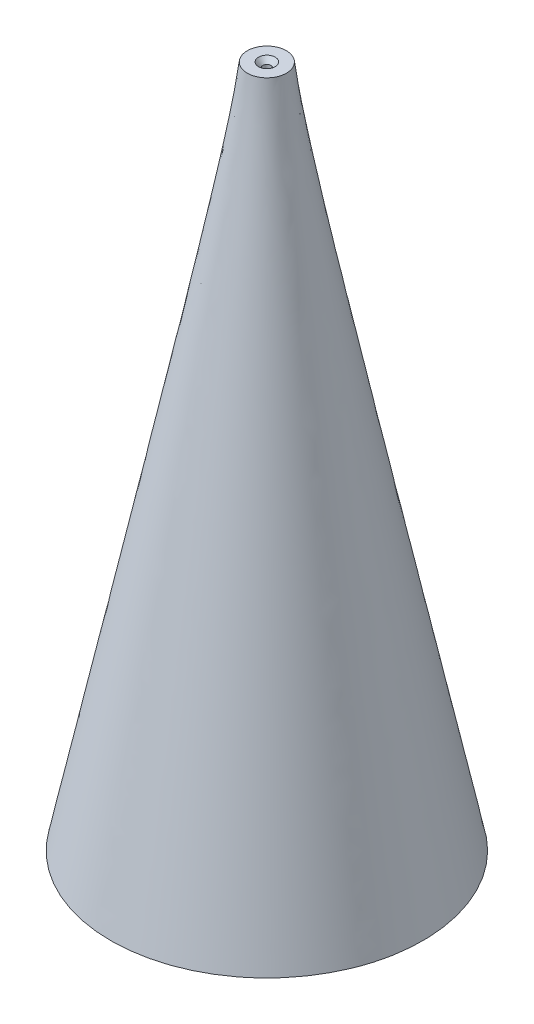
SolidWorks part; units mm, degrees
ref_plane "Front Plane" through (0, 0, 0) normal (0, 0, 1) x (1, 0, 0)
ref_plane "Top Plane" through (0, 0, 0) normal (0, 1, 0) x (1, 0, 0)
ref_plane "Right Plane" through (0, 0, 0) normal (1, 0, 0) x (0, 0, -1)
sketch "Sketch1" plane through (0, 0, 0) normal (0, 1, 0) x (1, 0, 0)
  circle A0 centre (0, 0) radius 40
  dimension "D1" = 80
ref_plane "Plane1" through (0, 100, 0) normal (0, 1, 0) x (1, 0, 0)
sketch "Sketch2" plane through (0, 100, 0) normal (0, 1, 0) x (1, 0, 0)
  circle A0 centre (0, 0) radius 5
  dimension "D1" = 10
ref_plane "Plane2" through (0, 175, 0) normal (0, 1, 0) x (1, 0, 0)
sketch "Sketch3" plane through (0, 175, 0) normal (0, 1, 0) x (1, 0, 0)
  circle A0 centre (0, 0) radius 5
  dimension "D1" = 10
loft "Loft2" add profiles "Sketch1", "Sketch3" connector at (-34.1187, 0, -20.8785) connector at (-4.763, 175, 1.5212)
sketch "Sketch4" plane through (0, 175, 0) normal (0, 1, 0) x (1, 0, 0)
  point P0 (0, 0)
hole_wizard "CSK for #1 Flat Head Socket Cap Screw1" positions "Sketch4" profile "Sketch5" countersink size "#1" standard "ANSI Inch" end condition through all
sketch "Sketch5" plane through (0, 175, 0) normal (1, 0, 0) x (0, 0, 1)
  line L0 (0, 0) -> (0, 175.0001)
  line L1 (0, 175.0001) -> (1.0287, 175.0001)
  line L2 (1.0287, 175.0001) -> (1.0287, 1.271)
  line L3 (1.0287, 1.271) -> (2.1336, 0)
  line L5 (2.1336, 0) -> (0, 0)
  line L6 (-1.0287, 1.271) -> (-2.1336, 0) construction
  line L11 (0, -6.35) -> (0, 107.95) construction
  dimension "Thru Hole Dia." = 2.0574
  dimension "Thru Hole Depth" = 175.0001
  dimension "Near C'Sink Dia." = 4.2672
  dimension "Near C'Sink Angle" = 82
